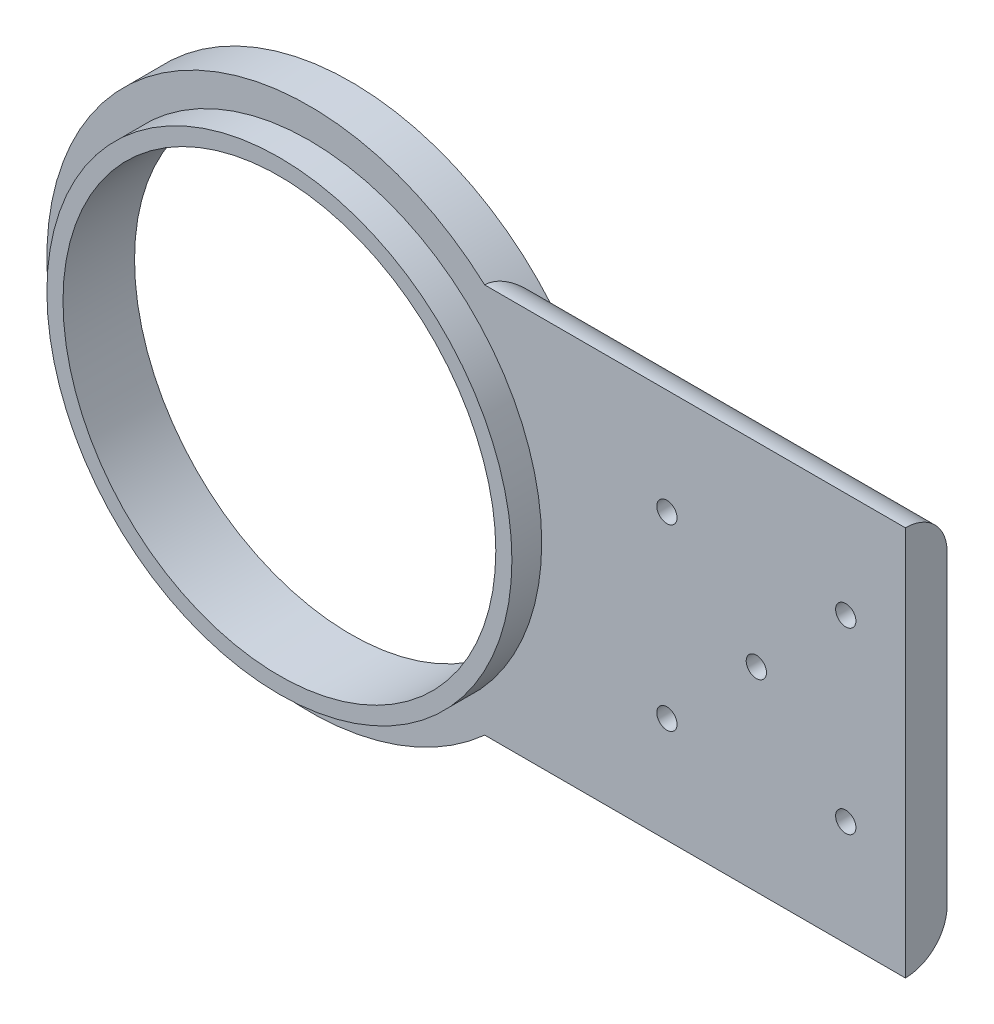
SolidWorks part; units mm, degrees
material "ABS"
ref_plane "Front" through (0, 0, 0) normal (0, 0, 1) x (1, 0, 0)
ref_plane "Top" through (0, 0, 0) normal (0, 1, 0) x (1, 0, 0)
ref_plane "Right" through (0, 0, 0) normal (1, 0, 0) x (0, 0, -1)
sketch "Croquis1" plane through (0, 0, 0) normal (0, 0, 1) x (1, 0, 0)
  circle A0 centre (0, 0) radius 36.3
  circle A1 centre (0, 0) radius 39
  dimension "D1" = 72.6
  dimension "D2" = 78
extrude "Saliente-Extruir1" add sketch "Croquis1" along normal mid plane 5
sketch "Croquis2" plane through (0, 0, -2.5) normal (0, 0, -1) x (-1, 0, 0)
  circle A0 centre (0, 0) radius 44
  circle A1 centre (0, 0) radius 36.3 construction
  circle A2 centre (0, 0) radius 36.3
  dimension "D1" = 88
extrude "Saliente-Extruir2" add sketch "Croquis2" along normal blind 7
sketch "Croquis3" plane through (0, 0, -9.5) normal (0, 0, -1) x (-1, 0, 0)
  line L0 (-29.4399, 32.7) -> (-100, 32.7)
  line L1 (-100, 32.7) -> (-100, -32.7)
  line L2 (-100, -32.7) -> (-29.4399, -32.7)
  line L3 (6.6, 0) -> (-6.6, 0) construction
  line L4 (0, 6.6) -> (0, -6.6) construction
  circle A0 centre (0, 0) radius 44 construction
  arc A1 (-29.4399, 32.7) -> (-29.4399, -32.7) centre (0, 0) ccw
  point P3 (0, 0)
  point P8 (0, 0)
  point P9 (0, 0)
  point P10 (-100, 0)
  circle M3 centre (0, 0) radius 44
  dimension "D1" = 65.4
  dimension "D2" = 100
extrude "Saliente-Extruir3" add sketch "Croquis3" against normal blind 7 contours L1 L2 L0 M3 region at (69.6148, 0, -9.5)
fillet "Redondeo1" radius 7 2 edges at (64.72, -32.7, -9.5) (64.72, 32.7, -9.5)
hole_wizard "Refrentado para tornillo con cabeza troncocónica de M31" positions "Croquis4" profile "Croquis6" counterbore size "M3" standard "Ansi Metric" end condition up to next
sketch "Croquis4" plane through (0, 0, -9.5) normal (0, 0, -1) x (-1, 0, 0)
  line L1 (-60, -15) -> (-90, -15) construction
  line L2 (-60, -15) -> (-60, 15) construction
  line L3 (-60, 15) -> (-90, 15) construction
  line L4 (-90, -15) -> (-90, 15) construction
  line L5 (-60, -15) -> (-90, 15) construction
  line L6 (-60, 15) -> (-90, -15) construction
  line L7 (6.6, 0) -> (-6.6, 0) construction
  line L8 (-100, 25.7) -> (-100, -25.7) construction
  point P1 (-75, 0)
  point P2 (-90, 15)
  point P29 (-60, -15)
  point P30 (-60, 15)
  point P31 (-90, -15)
  dimension "D1" = 30
  dimension "D2" = 25
sketch "Croquis6" plane through (75, 0, -9.5) normal (1, 0, 0) x (0, 1, 0)
  line L0 (0, 0) -> (0, 7)
  line L1 (0, 7) -> (1.7, 7)
  line L3 (1.7, 7) -> (1.7, 2.4)
  line L4 (1.7, 2.4) -> (3.5, 2.4)
  line L5 (3.5, 2.4) -> (3.5, 0)
  line L7 (3.5, 0) -> (0, 0)
  line L11 (0, -6.35) -> (0, 107.95) construction
  dimension "Diámetro de taladro hasta el siguiente" = 3.4
  dimension "Profundidad de taladro hasta el siguiente" = 7
  dimension "Diámetro de refrentado" = 7
  dimension "Profundidad de refrentado" = 2.4
